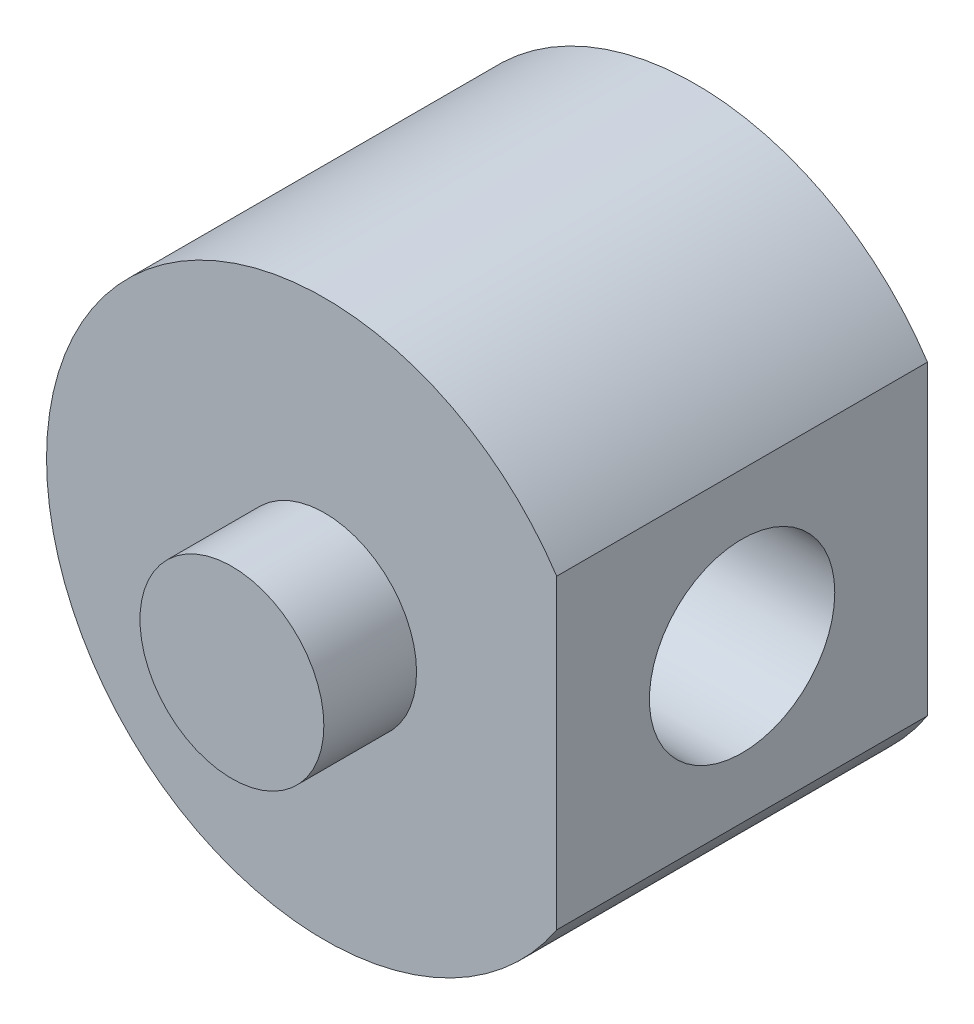
SolidWorks part; units mm, degrees
material "1023 Carbon Steel Sheet (SS)"
ref_plane "Front Plane" through (0, 0, 0) normal (0, 0, 1) x (1, 0, 0)
ref_plane "Top Plane" through (0, 0, 0) normal (0, 1, 0) x (1, 0, 0)
ref_plane "Right Plane" through (0, 0, 0) normal (1, 0, 0) x (0, 0, -1)
sketch "Sketch3" plane through (0, 0, 0) normal (0, 0, 1) x (1, 0, 0)
  line L0 (3.13, 2.0653) -> (3.13, -2.0653)
  line L1 (0, 0) -> (-3.75, 0) construction
  circle A0 centre (0, 0) radius 3.75
  point P5 (-3.75, 0)
  dimension "D1" = 7.5
  dimension "D2" = 6.88
extrude "Boss-Extrude1" add sketch "Sketch3" along normal mid plane 5 contours L0 A0 region at (-0.1384, 0, 0)
sketch "Sketch4" plane through (0, 0, 2.5) normal (0, 0, 1) x (1, 0, 0)
  circle A0 centre (0, 0) radius 1.24
  dimension "D1" = 2.48
extrude "Boss-Extrude2" add sketch "Sketch4" along normal blind 1.25 contours A0
mirror "Mirror1" about plane through (0, 0, 0) normal (0, 0, 1) of "Boss-Extrude2"
sketch "Sketch5" plane through (3.13, 0, 0) normal (1, 0, 0) x (0, 0, -1)
  circle A0 centre (0, 0) radius 1.25
  dimension "D1" = 2.5
extrude "Cut-Extrude2" cut sketch "Sketch5" against normal through all
sketch "Sketch7" plane through (3.13, 0, 0) normal (1, 0, 0) x (0, 0, -1)
  circle A0 centre (0, 0) radius 1.875
  dimension "D1" = 3.75
extrude "Cut-Extrude3" cut sketch "Sketch7" against normal blind 8.25
sketch "Sketch8" plane through (3.13, 0, 0) normal (1, 0, 0) x (0, 0, -1)
  circle A0 centre (0, 0) radius 1.875
extrude "Boss-Extrude3" add sketch "Sketch8" against normal blind 4.4
extrude "Cut-Extrude4" cut sketch "Sketch5<3>" against normal through all
sketch "Sketch5<3>" plane through (3.13, 0, 0) normal (1, 0, 0) x (0, 0, -1) same geometry as "Sketch5"
